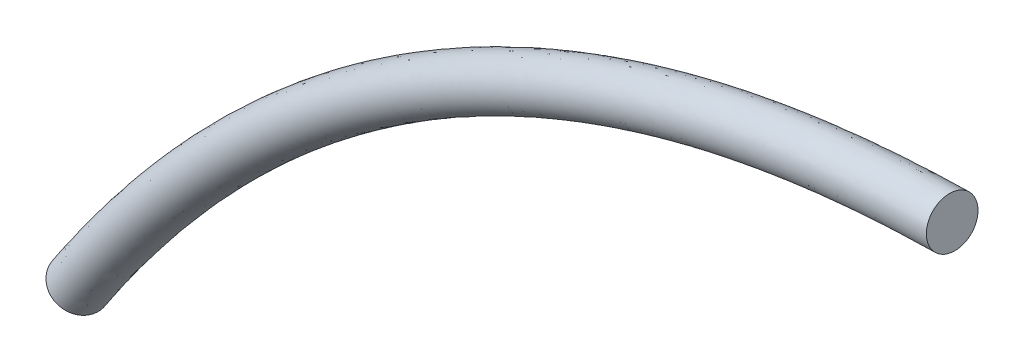
SolidWorks part; units mm, degrees
material "Custom Plastic"
ref_plane "X-Y Datum" through (0, 0, 0) normal (0, 0, 1) x (1, 0, 0)
ref_plane "X-Z Datum" through (0, 0, 0) normal (0, 1, 0) x (1, 0, 0)
ref_plane "Y-Z Datum" through (0, 0, 0) normal (1, 0, 0) x (0, 0, -1)
sketch3d "3DSketch1"
  circle A0 centre (-244.2256, -166.5107, 163.3218) radius 2.9 construction
  circle A1 centre (-70.1324, -53.4906, 183.2483) radius 2.5781 construction
  circle A3 centre (-244.2256, -166.5107, 163.3218) radius 3.475 construction
  spline S0 degree 2 poles (-244.2256, -166.5107, 163.3218) (-168.0574, -59.5751, 178.3266) (-56.5066, -52.2024, 183.9814) knots 0 0 0 1 1 1
  point P0 (-244.2256, -166.5107, 163.3218)
  point P1 (-70.1324, -53.4906, 183.2483)
  point P4 (-246.0339, -168.7779, 163.3218)
  point P8 (-72.6964, -53.7601, 183.2483)
  point P10 (-54.8428, -51.8403, 187.2568)
  point P12 (-56.5066, -52.2024, 183.9814)
  point P16 (-246.3925, -169.2274, 163.3218)
sweep "Sweep1" add path "3DSketch1" circular profile diameter 9.398 parameters "D3"=9.398
